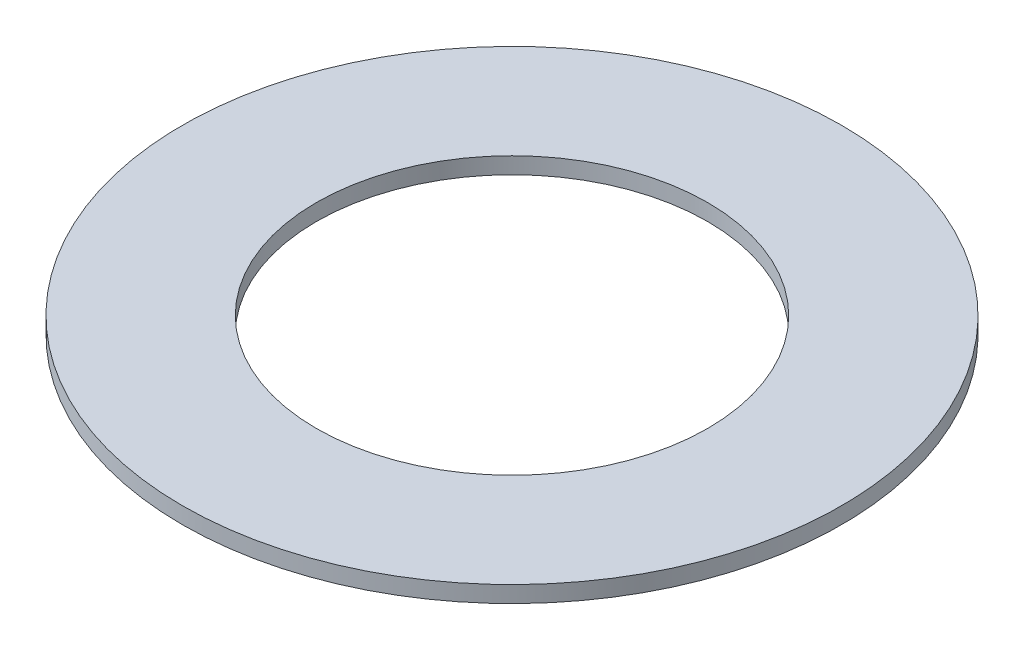
SolidWorks part; units mm, degrees
ref_plane "Front Plane" through (0, 0, 0) normal (0, 0, 1) x (1, 0, 0)
ref_plane "Top Plane" through (0, 0, 0) normal (0, 1, 0) x (1, 0, 0)
ref_plane "Right Plane" through (0, 0, 0) normal (1, 0, 0) x (0, 0, -1)
sketch "Sketch1" plane through (0, 0, 0) normal (0, 1, 0) x (1, 0, 0)
  circle A0 centre (0, 0) radius 80
  dimension "FLANGE_OD" = 160
extrude "Boss-Extrude1" add sketch "Sketch1" along normal blind 4
sketch "Sketch2" plane through (0, 0, 0) normal (0, 1, 0) x (1, 0, 0)
  circle A0 centre (0, 0) radius 47.5
  dimension "BORE_D" = 95
extrude "Cut-Extrude1" cut sketch "Sketch2" along normal through all
sketch "Sketch3" plane through (0, 4, 0) normal (0, 1, 0) x (1, 0, 0)
  circle A0 centre (0, 0) radius 34.7933 construction
  circle A1 centre (-34.7933, 0) radius 2.9737
  dimension "BOLT_D" = 5.9474
  dimension "BOLT_PCD" = 69.5867
extrude "Cut-Extrude2" cut sketch "Sketch3" against normal blind 2.8859 rebuild error yes
pattern_circular "CirPattern1" count 8 over 360 rebuild error yes
